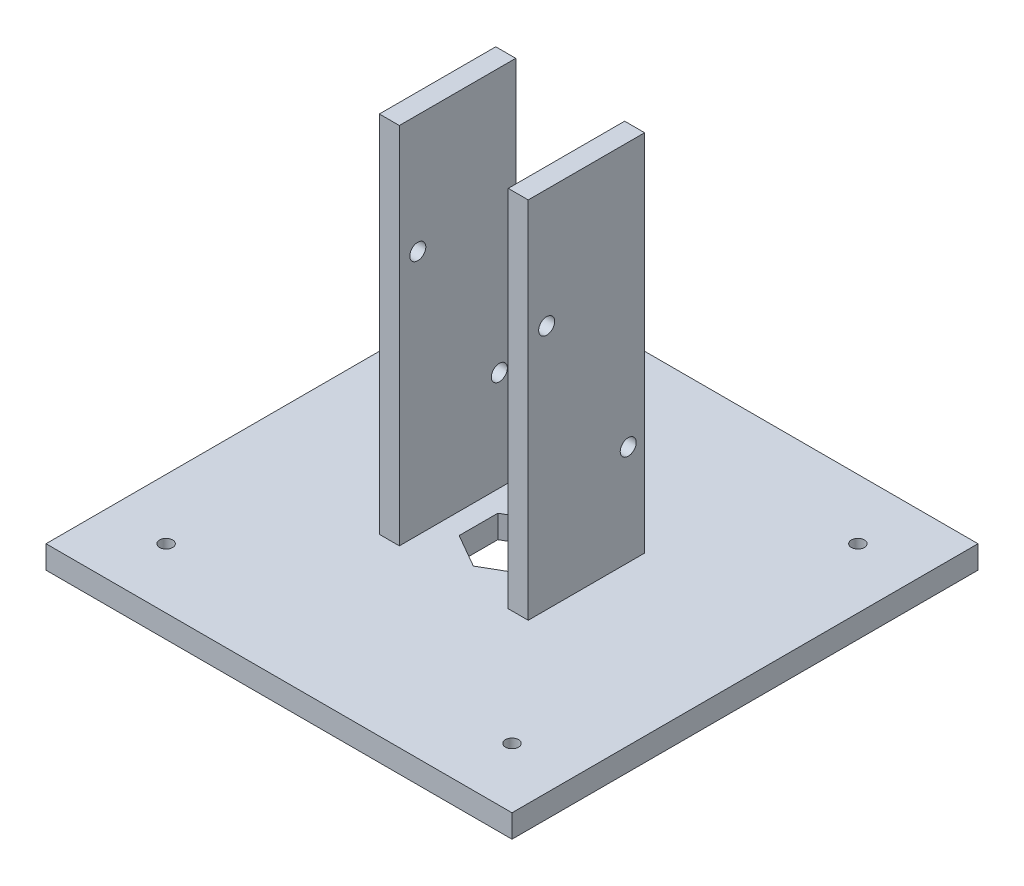
SolidWorks part; units mm, degrees
ref_plane "Front Plane" through (0, 0, 0) normal (0, 0, 1) x (1, 0, 0)
ref_plane "Top Plane" through (0, 0, 0) normal (0, 1, 0) x (1, 0, 0)
ref_plane "Right Plane" through (0, 0, 0) normal (1, 0, 0) x (0, 0, -1)
sketch "Sketch2" plane through (0, 0, 0) normal (0, 1, 0) x (1, 0, 0)
  line L0 (0, 0) -> (0, 60.325) construction
  line L1 (0, 13.4915) -> (-11.684, 6.7458)
  line L2 (-11.684, 6.7458) -> (-11.684, -6.7458)
  line L3 (-11.684, -6.7458) -> (0, -13.4915)
  line L4 (0, -13.4915) -> (11.684, -6.7458)
  line L5 (11.684, -6.7458) -> (11.684, 6.7458)
  line L6 (11.684, 6.7458) -> (0, 13.4915)
  line L7 (0, 0) -> (-60.325, 0) construction
  line L8 (0, 0) -> (60.325, 0) construction
  line L9 (0, 0) -> (0, -60.325) construction
  line L27 (81.28, -81.28) -> (-81.28, -81.28)
  line L28 (81.28, -81.28) -> (81.28, 81.28)
  line L29 (81.28, 81.28) -> (-81.28, 81.28)
  line L30 (-81.28, -81.28) -> (-81.28, 81.28)
  line L31 (81.28, -81.28) -> (-81.28, 81.28) construction
  line L32 (81.28, 81.28) -> (-81.28, -81.28) construction
  line L33 (-60.325, -60.325) -> (60.325, -60.325) construction
  line L34 (-60.325, -60.325) -> (-60.325, 60.325) construction
  line L35 (-60.325, 60.325) -> (60.325, 60.325) construction
  line L36 (60.325, -60.325) -> (60.325, 60.325) construction
  line L37 (-60.325, -60.325) -> (60.325, 60.325) construction
  line L38 (-60.325, 60.325) -> (60.325, -60.325) construction
  circle A0 centre (0, 0) radius 60.325 construction
  circle A1 centre (0, 0) radius 11.684 construction
  circle A2 centre (60.325, 60.325) radius 2.286
  circle A3 centre (60.325, -60.325) radius 2.286
  circle A4 centre (-60.325, -60.325) radius 2.286
  circle A5 centre (-60.325, 60.325) radius 2.286
  dimension "D1" = 120.65
  dimension "D13" = 120.65
  dimension "D14" = 4.572
  dimension "D15" = 4.572
  dimension ".18" = 4.572
  dimension "D17" = 4.572
  dimension "D2" = 23.368
  dimension "D11" = 162.56
  dimension "D12" = 162.56
extrude "Boss-Extrude1" add sketch "Sketch2" along normal blind 8 contours A0 | A0 | A0 | A0 L6 L5 L4 L3 L2 L1 | L34 L33 L36 L35 | A0 region at (0, 0, 78.9811)
sketch "Sketch7" plane through (0, 8, 0) normal (0, 1, 0) x (1, 0, 0)
  line L0 (22.479, 0) -> (-22.479, 0) construction
  line L2 (-18.9936, -20.3024) -> (-25.9644, -20.3024)
  line L9 (-18.9936, -20.3024) -> (-18.9936, 20.3024)
  line L10 (-18.9936, 20.3024) -> (-25.9644, 20.3024)
  line L11 (-25.9644, -20.3024) -> (-25.9644, 20.3024)
  line L12 (-18.9936, -20.3024) -> (-25.9644, 20.3024) construction
  line L13 (-18.9936, 20.3024) -> (-25.9644, -20.3024) construction
  point P0 (-22.479, 0)
  point P8 (0, 0)
  dimension "D1" = 40.6049
  dimension "D2" = 6.9708
  dimension "D3" = 22.479
extrude "Boss-Extrude3" add sketch "Sketch7" along normal blind 127 contours L9 L2 L11 L10
ref_plane "Plane1" through (0, 0, 0) normal (1, 0, 0) x (0, 0, -1)
mirror "Mirror1" about plane through (0, 0, 0) normal (1, 0, 0) of "Boss-Extrude3"
sketch "Sketch8" plane through (25.9644, 0, -7.2061) normal (-1, 0, 0) x (0, 0, 1)
  line L0 (-11.4417, 8.762) -> (25.1343, 8.762) construction
  line L1 (7.2061, 135) -> (7.2061, 8) construction
  line L2 (-13.0964, 135) -> (27.5085, 135) construction
  line L3 (27.5085, 8) -> (-13.0964, 8) construction
  circle A0 centre (21.0703, 93.725) radius 2.794
  circle A1 centre (-7.3777, 42.925) radius 2.794
  dimension "D1" = 5.588
  dimension "D2" = 5.588
  dimension "D3" = 14.5837
  dimension "D4" = 50.8
extrude "Cut-Extrude1" cut sketch "Sketch8" along normal through all
